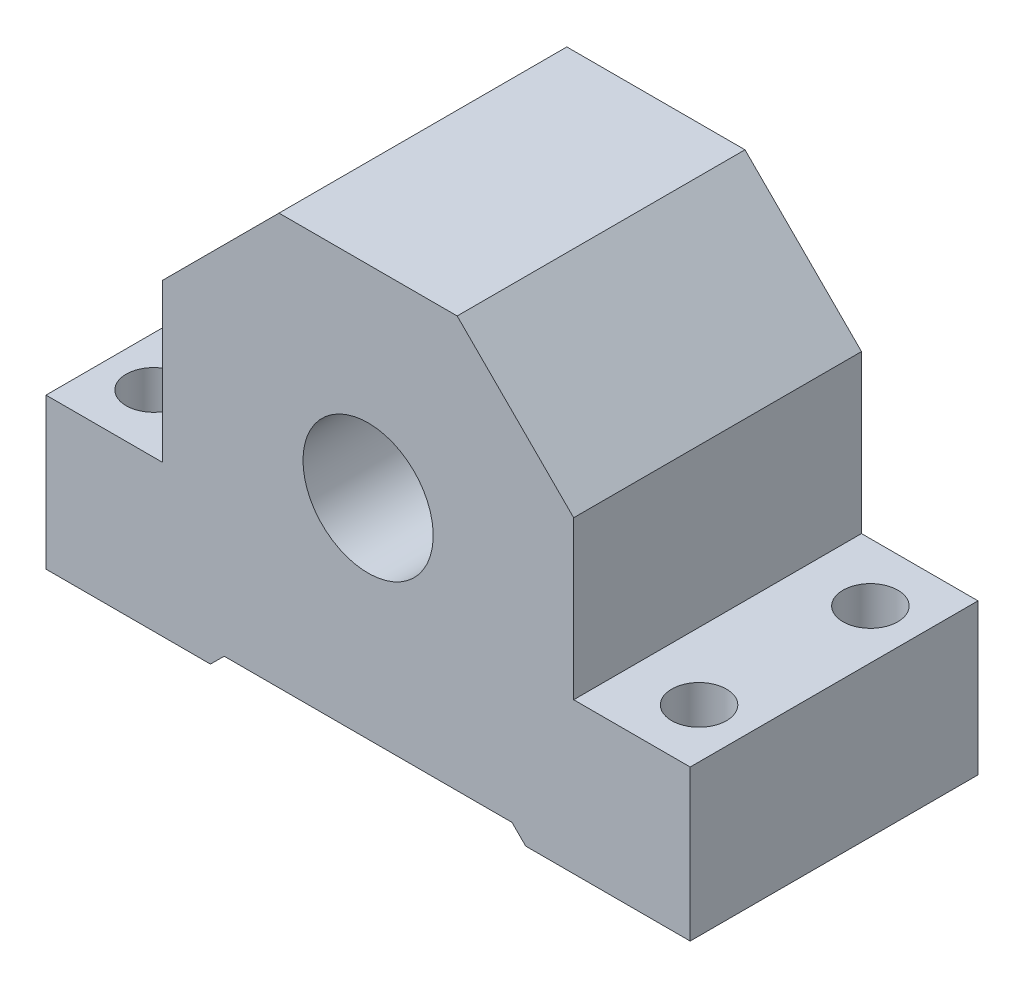
SolidWorks part; units mm, degrees
ref_plane "Płaszczyzna przednia" through (0, 0, 0) normal (0, 0, 1) x (1, 0, 0)
ref_plane "Płaszczyzna górna" through (0, 0, 0) normal (0, 1, 0) x (1, 0, 0)
ref_plane "Płaszczyzna prawa" through (0, 0, 0) normal (1, 0, 0) x (0, 0, -1)
sketch "Szkic1" plane through (0, 0, 0) normal (0, 0, 1) x (1, 0, 0)
  line L0 (-47, 11) -> (-30, 11)
  line L2 (47, -11) -> (47, 11)
  line L4 (-47, -11) -> (-47, 11)
  line L5 (47, -11) -> (-47, 11) construction
  line L6 (47, 11) -> (-47, -11) construction
  line L7 (-30, 11) -> (-30, 34)
  line L8 (-30, 34) -> (-13, 51)
  line L9 (-13, 51) -> (13, 51)
  line L10 (13, 51) -> (30, 34)
  line L11 (30, 34) -> (30, 11)
  line L12 (30, 11) -> (47, 11)
  line L13 (-47, -11) -> (-23, -11)
  line L14 (-23, -11) -> (-21, -9)
  line L15 (-21, -9) -> (21, -9)
  line L16 (21, -9) -> (23, -11)
  line L17 (23, -11) -> (47, -11)
  point P0 (0, 0)
  point P18 (35, -11)
  dimension "D1" = 94
  dimension "D2" = 26
  dimension "D3" = 26
  dimension "D4" = 135
  dimension "D5" = 135
  dimension "D6" = 17
  dimension "D7" = 26
  dimension "D8" = 2
  dimension "D9" = 135
  dimension "D10" = 135
  dimension "D11" = 62
  dimension "D12" = 22
  dimension "D13" = 60
  dimension "D14" = 17
  dimension "D15" = 17
extrude "Dodanie-wyciągnięcie1" add sketch "Szkic1" along normal blind 42
sketch "Szkic2" plane through (0, 0, 0) normal (0, 0, -1) x (-1, 0, 0)
  line L0 (-13, 51) -> (13, 51) construction
  circle A0 centre (0, 21.5) radius 9.5
  dimension "D1" = 29.5
extrude "Wytnij-wyciągnięcie1" cut sketch "Szkic2" against normal blind 42
sketch "Szkic3" plane through (0, 11, 0) normal (0, 1, 0) x (1, 0, 0)
  line L0 (-30, 0) -> (-47, 0) construction
  line L1 (-47, -42) -> (-47, 0) construction
  line L2 (-30, -42) -> (-47, -42) construction
  line L3 (47, -42) -> (47, 0) construction
  line L6 (47, 0) -> (30, 0) construction
  line L7 (47, -42) -> (30, -42) construction
  circle A0 centre (-39.8, -8.5) radius 4
  circle A1 centre (-39.8, -33.5) radius 4
  circle A2 centre (39.8, -33.5) radius 4
  circle A3 centre (39.8, -8.5) radius 4
  point P18 (42.925, 0)
  point P19 (40.5292, -8.6715)
  point P22 (-43.8, -8.5)
  dimension "D1" = 8.5
  dimension "D2" = 7.2
  dimension "D3" = 8.5
  dimension "D4" = 7.2
  dimension "D5" = 7.2
  dimension "D6" = 8.5
  dimension "D7" = 7.2
  dimension "D8" = 8.5
extrude "Wytnij-wyciągnięcie2" cut sketch "Szkic3" against normal blind 22
